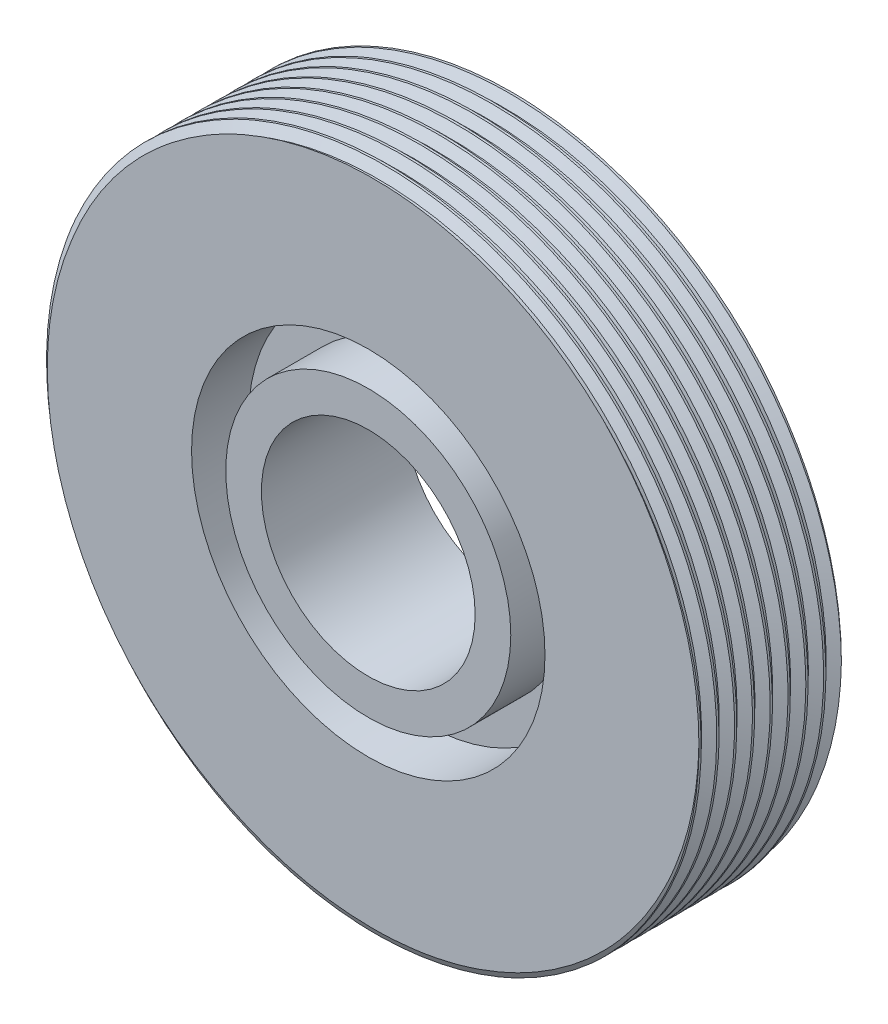
SolidWorks part; units mm, degrees
ref_plane "Front Plane" through (0, 0, 0) normal (0, 0, 1) x (1, 0, 0)
ref_plane "Top Plane" through (0, 0, 0) normal (0, 1, 0) x (1, 0, 0)
ref_plane "Right Plane" through (0, 0, 0) normal (1, 0, 0) x (0, 0, -1)
sketch "Sketch3" plane through (0, 0, 0) normal (0, 0, 1) x (1, 0, 0)
  circle A3 centre (8.3476, 27.7238) radius 14.732
  dimension "D1" = 29.464
extrude "Boss-Extrude1" add sketch "Sketch3" against normal blind 6.35 contours A3 region at (8.3476, 27.7238, 0)
sketch "Sketch11" plane through (0, 0, 0) normal (0, 0, 1) x (1, 0, 0)
  circle A0 centre (8.3476, 27.7238) radius 4.7625
extrude "Cut-Extrude3" cut sketch "Sketch11" against normal through all
sketch "Sketch12" plane through (0, 0, 0) normal (0, 0, 1) x (1, 0, 0)
  circle A0 centre (8.3476, 27.7238) radius 6.35
  circle A1 centre (8.3476, 27.7238) radius 7.874
  dimension "D1" = 15.748
  dimension "D2" = 1.524
extrude "Cut-Extrude4" cut sketch "Sketch12" against normal blind 2.54
thread "Thread1" pitch 0.7937 method cut profile "Thread Profile1" start angle 0, offset 0.7937, length 7.62, pitch 0.7937, diameter 29.464
ref_plane "Plane1" through (23.0796, 27.7238, -7.1437) normal (0, -1, 0) x (1, 0, 0)
sketch "Thread Profile1" plane through (23.0796, 27.7238, -7.1437) normal (0, -1, 0) x (1, 0, 0)
  line L0 (0, 0) -> (0, 0.7937) construction
  line L11 (0, 0) -> (0, 0.6945)
  line L12 (0, 0.6945) -> (-0.4296, 0.4465)
  line L13 (-0.4296, 0.4465) -> (-0.4296, 0.248)
  line L15 (-0.4296, 0.248) -> (0, 0)
  line L17 (-0.4296, 0.3473) -> (0, 0.3473) construction
  point P2 (0, 0)
  dimension "Pitch" = 0.7937
  dimension "Profile_Angle" = 60
  dimension "Profile_Land" = 0.1984
  dimension "Profile_Height" = 0.4296
